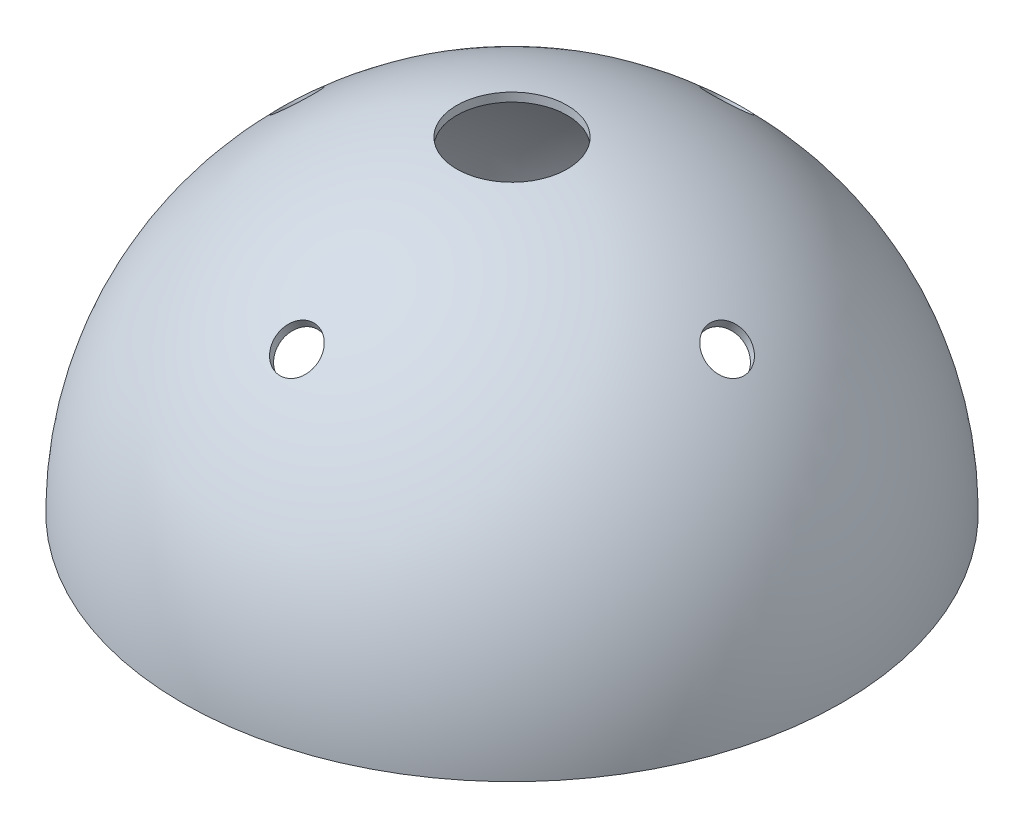
SolidWorks part; units mm, degrees
ref_plane "Front Plane" through (0, 0, 0) normal (0, 0, 1) x (1, 0, 0)
ref_plane "Top Plane" through (0, 0, 0) normal (0, 1, 0) x (1, 0, 0)
ref_plane "Right Plane" through (0, 0, 0) normal (1, 0, 0) x (0, 0, -1)
sketch "Sketch6" plane through (0, 0, 0) normal (0, 0, 1) x (1, 0, 0)
  line L0 (0, 37.9734) -> (0, 0)
  line L1 (0, 0) -> (37.9734, 0)
  arc A0 (0, 37.9734) -> (37.9734, 0) centre (0, 0) cw
  dimension "D1" = 37.9734
revolve "Revolve3" add sketch "Sketch6" angle 360 about L0
sketch "Sketch16" plane through (0, 0, 0) normal (0, 0, 1) x (1, 0, 0)
  line L5 (0, 33.8844) -> (-6.3629, 33.8844)
  line L6 (-6.3629, 33.8844) -> (-6.3629, 45.9817)
  line L7 (-6.3629, 45.9817) -> (0, 45.9817)
  line L8 (0, 45.9817) -> (0, 33.8844)
ref_axis "Axis1" through (0, 49.2808, 0) along (0, -1, 0)
ref_axis "Axis2" through (41.7708, 0, 0) along (-1, 0, 0)
sketch "Sketch18" plane through (0, 0, 0) normal (1, 0, 0) x (0, 0, -1)
  line L0 (0, 0) -> (0, -19.9503)
  line L1 (0, 49.2808) -> (0, -23.299) construction
  line L3 (0, -19.9503) -> (38.2775, -19.9503)
  line L4 (38.2775, -19.9503) -> (28.3519, -19.9503)
  line L5 (0, -19.9503) -> (-41.192, -19.9503)
sketch "Sketch21" plane through (0, 0, 0) normal (0, 0, 1) x (1, 0, 0)
  line L0 (0, 0) -> (0, 36.9972)
  line L1 (0, 45.9817) -> (0, 33.8844) construction
  line L2 (0, 0) -> (-36.9864, 0)
  line L3 (41.7708, 0) -> (-41.7708, 0) construction
  line L4 (0.0054, 0.0054) -> (0, 9.202)
  line L5 (0, 9.202) -> (2.484, 9.202)
  line L6 (2.484, 9.202) -> (2.484, 44.2445)
  line L7 (2.484, 44.2445) -> (0, 44.2445)
  line L8 (0, 44.2445) -> (0, 9.202)
  arc A0 (0, 36.9972) -> (-36.9864, 0) centre (0.0054, 0.0054) ccw
revolve "Cut-Revolve16" cut sketch "Sketch21" angle 360 about L0
pattern_circular "CirPattern4" count 2 every 27 about axis through (0, -19.9503, 0) along (0, 0, 1) of "Cut-Revolve16"
pattern_circular "CirPattern5" count 4 every 90 about axis through (0, 49.2808, 0) along (0, -1, 0) of "CirPattern4"
sketch "Sketch22" plane through (0, 0, 0) normal (1, 0, 0) x (0, 0, -1)
  line L0 (0, 0) -> (0, 36.9872)
  line L1 (0, 33.8844) -> (0, 45.9817) construction
  line L2 (0, 0) -> (-37.0145, 0)
  line L3 (-37.9734, 0) -> (37.9734, 0) construction
  arc A0 (0, 36.9872) -> (-37.0145, 0) centre (-0.0137, -0.0137) ccw
revolve "Cut-Revolve17" cut sketch "Sketch22" angle 360 about L0
revolve "Cut-Revolve18" cut sketch "Sketch16" angle 360 about L8
